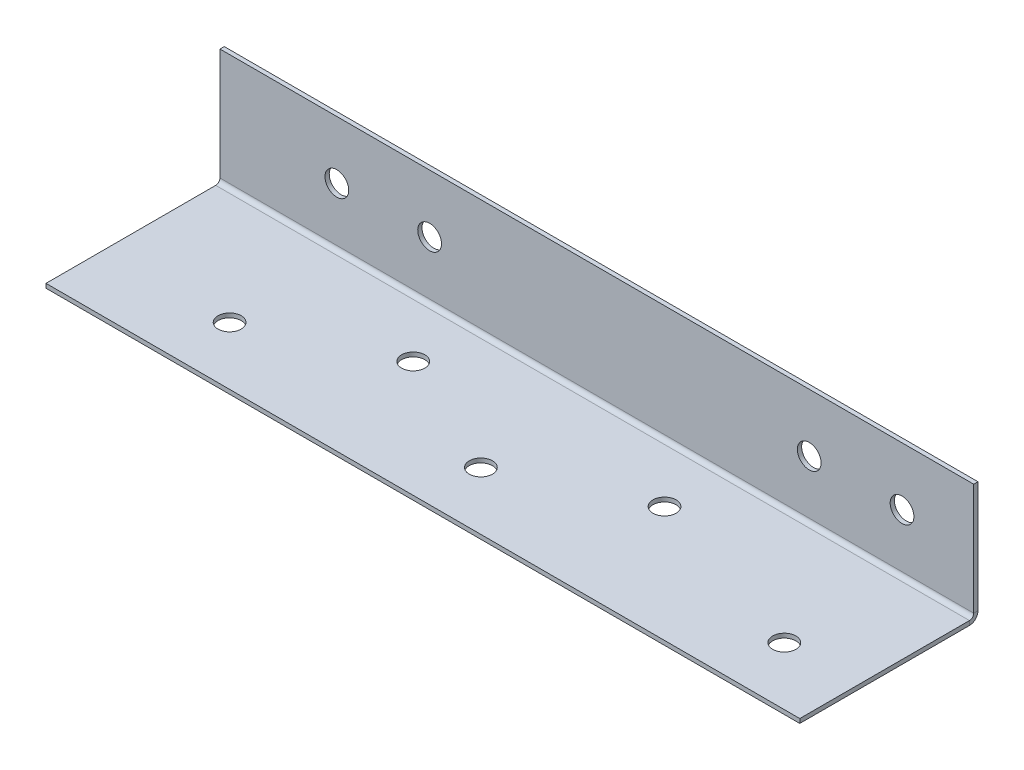
SolidWorks part; units mm, degrees
note: The reader was unsure of these and kept them because the rebuilt part matched: flange length of "Edge-Flange1".
ref_plane "Front Plane" through (0, 0, 0) normal (0, 0, 1) x (1, 0, 0)
ref_plane "Top Plane" through (0, 0, 0) normal (0, 1, 0) x (1, 0, 0)
ref_plane "Right Plane" through (0, 0, 0) normal (1, 0, 0) x (0, 0, -1)
sketch "Sketch1" plane through (0, 0, 0) normal (0, 1, 0) x (1, 0, 0)
  line L1 (-65, -15) -> (65, -15)
  line L2 (-65, -15) -> (-65, 15)
  line L3 (-65, 15) -> (65, 15)
  line L4 (65, -15) -> (65, 15)
  line L5 (-65, -15) -> (65, 15) construction
  line L6 (-65, 15) -> (65, -15) construction
  circle A0 centre (0, -5) radius 2
  circle A1 centre (-21.6667, 5) radius 2
  circle A2 centre (-43.3333, -5) radius 2
  circle A3 centre (52.33, -5) radius 2
  circle A4 centre (21.67, 5) radius 2
  point P0 (0, 0)
  dimension "D3" = 4
  dimension "D4" = 4
  dimension "D5" = 4
  dimension "D6" = 4
  dimension "D7" = 4
  dimension "D1" = 130
  dimension "D2" = 30
  dimension "D8" = 21.6667
  dimension "D9" = 43.3333
  dimension "D10" = 43.33
  dimension "D11" = 12.67
  dimension "D12" = 10
  dimension "D13" = 10
  dimension "D14" = 10
  dimension "D15" = 10
  dimension "D16" = 10
base flange "Base-Flange1" sketch "Sketch1" thickness 0.7366 reverse thickness direction no parameters "D1"=0.7366
edge flange "Edge-Flange1" sketch "Sketch8" flange angle 90 flange length 20.7366 flange position material outside bend radius 0.7366 thickness 0.7366 relief rectangular parameters "D6"=10
sketch "Sketch8" plane through (0, 0, -15) normal (0, 0, -1) x (-1, 0, 0)
  line L0 (-65, 0) -> (65, 0) construction
  line L1 (-65, 0) -> (65, 0)
  line L2 (-65, 0) -> (-65, 20)
  line L3 (-65, 20) -> (65, 20)
  line L4 (65, 20) -> (65, 0)
  dimension "D1" = 20
bend "EdgeBend1" bend radius 0.7366 bend angle 90 parameters "D5"=1
extrude "Cut-Extrude1" cut sketch "Sketch9" against normal through all normal cut yes
sketch "Sketch9" plane through (-5.9759, -11.7404, -216.4732) normal (0, 0, -1) x (-1, 0, 0)
  circle A3 centre (-42.6105, 21.7404) radius 2.05
  circle A6 centre (-58.6105, 21.7404) radius 2.05
  circle A9 centre (22.8627, 21.7404) radius 2.05
  circle A12 centre (38.8627, 21.7404) radius 2.05
sketch "Bend-Lines1" [suppressed] plane through (0, 0, 0) normal (0, 1, 0) x (1, 0, 0)
sketch "Bounding-Box1" [suppressed] plane through (0, 0, 0) normal (0, 1, 0) x (1, 0, 0)
sketch "Sketch10" [suppressed] plane through (0, 0, 0) normal (0, 1, 0) x (1, 0, 0)
  line L1 (60.563, 15.3312) -> (60.563, 14.9312)
  line L2 (65, 15.3312) -> (-65, 15.3312)
  line L3 (60.563, 15.3312) -> (55.563, 15.3312)
  line L4 (65, 14.9312) -> (-65, 14.9312)
  line L5 (60.563, 14.9312) -> (55.563, 14.9312)
  line L6 (55.563, 15.3312) -> (55.563, 14.9312)
  line L7 (50.563, 15.3312) -> (50.563, 14.9312)
  line L8 (45.563, 15.3312) -> (45.563, 14.9312)
  line L9 (40.563, 15.3312) -> (40.563, 14.9312)
  line L10 (35.563, 15.3312) -> (35.563, 14.9312)
  line L11 (30.563, 15.3312) -> (30.563, 14.9312)
  line L12 (25.563, 15.3312) -> (25.563, 14.9312)
  line L13 (20.563, 15.3312) -> (20.563, 14.9312)
  line L14 (15.563, 15.3312) -> (15.563, 14.9312)
  line L15 (10.563, 15.3312) -> (10.563, 14.9312)
  line L16 (5.563, 15.3312) -> (5.563, 14.9312)
  line L17 (0.563, 15.3312) -> (0.563, 14.9312)
  line L18 (-4.437, 15.3312) -> (-4.437, 14.9312)
  line L19 (-9.437, 15.3312) -> (-9.437, 14.9312)
  line L20 (-14.437, 15.3312) -> (-14.437, 14.9312)
  line L21 (-19.437, 15.3312) -> (-19.437, 14.9312)
  line L22 (-24.437, 15.3312) -> (-24.437, 14.9312)
  line L23 (-29.437, 15.3312) -> (-29.437, 14.9312)
  line L24 (-34.437, 15.3312) -> (-34.437, 14.9312)
  line L25 (-39.437, 15.3312) -> (-39.437, 14.9312)
  line L26 (-44.437, 15.3312) -> (-44.437, 14.9312)
  line L27 (-49.437, 15.3312) -> (-49.437, 14.9312)
  line L28 (-54.437, 15.3312) -> (-54.437, 14.9312)
  line L29 (-59.437, 15.3312) -> (-59.437, 14.9312)
  line L30 (-64.437, 15.3312) -> (-64.437, 14.9312)
  line L31 (50.563, 15.3312) -> (45.563, 15.3312)
  line L32 (50.563, 14.9312) -> (45.563, 14.9312)
  line L33 (40.563, 14.9312) -> (35.563, 14.9312)
  line L34 (40.563, 15.3312) -> (35.563, 15.3312)
  line L35 (30.563, 15.3312) -> (25.563, 15.3312)
  line L36 (30.563, 14.9312) -> (25.563, 14.9312)
  line L37 (20.563, 14.9312) -> (15.563, 14.9312)
  line L38 (20.563, 15.3312) -> (15.563, 15.3312)
  line L39 (10.563, 15.3312) -> (5.563, 15.3312)
  line L40 (10.563, 14.9312) -> (5.563, 14.9312)
  line L41 (0.563, 14.9312) -> (-4.437, 14.9312)
  line L42 (0.563, 15.3312) -> (-4.437, 15.3312)
  line L43 (-9.437, 14.9312) -> (-14.437, 14.9312)
  line L44 (-9.437, 15.3312) -> (-14.437, 15.3312)
  line L45 (-19.437, 15.3312) -> (-24.437, 15.3312)
  line L46 (-19.437, 14.9312) -> (-24.437, 14.9312)
  line L47 (-29.437, 14.9312) -> (-34.437, 14.9312)
  line L48 (-29.437, 15.3312) -> (-34.437, 15.3312)
  line L49 (-39.437, 15.3312) -> (-44.437, 15.3312)
  line L50 (-39.437, 14.9312) -> (-44.437, 14.9312)
  line L51 (-49.437, 14.9312) -> (-54.437, 14.9312)
  line L52 (-49.437, 15.3312) -> (-54.437, 15.3312)
  line L53 (-59.437, 15.3312) -> (-64.437, 15.3312)
  line L54 (-59.437, 14.9312) -> (-64.437, 14.9312)
  dimension "D1" = 0.2
  dimension "D2" = 0.2
  dimension "D3" = 26
extrude "Cut-Extrude2" [suppressed] cut sketch "Sketch10" against normal blind 10
sheet metal parameters "Sheet-Metal1" thickness 0.7366 parameters "D1"=0.7366
flat pattern "Flat-Pattern1" [suppressed]
sketch "Bend-Lines2" plane through (0, 0, 0) normal (0, 1, 0) x (1, 0, 0)
sketch "Bounding-Box2" [suppressed] plane through (0, 0, 0) normal (0, 1, 0) x (1, 0, 0)
sheet metal parameters "Sheet-Metal2" thickness 0.7366 parameters "D1"=0.7366
flat pattern "Flat-Pattern1" [suppressed]
sketch "Bend-Lines2" plane through (0, 0, 0) normal (0, 1, 0) x (1, 0, 0)
sketch "Bounding-Box2" [suppressed] plane through (0, 0, 0) normal (0, 1, 0) x (1, 0, 0)
bend of the flat pattern "Flatten-<EdgeBend1>1"
sheet metal parameters "Sheet-Metal3" thickness 0.7366 parameters "D1"=0.7366
flat pattern "Flat-Pattern1"
sketch "Bend-Lines2" plane through (0, 0, 0) normal (0, 1, 0) x (1, 0, 0)
  line L0 (65, 15.1312) -> (-65, 15.1312) construction
  line L1 (65, 15.1312) -> (-65, 15.1312) construction
sketch3d "Bounding-Box2" [suppressed]
  line L0 (65, 35.2624, 0) -> (-65, 35.2624, 0) construction
  line L1 (65, -15, 0) -> (-65, -15, 0) construction
  line L2 (65, 35.2624, 0) -> (65, -15, 0) construction
  line L3 (-65, 35.2624, 0) -> (-65, -15, 0) construction
bend of the flat pattern "Flatten-<EdgeBend1>1"
